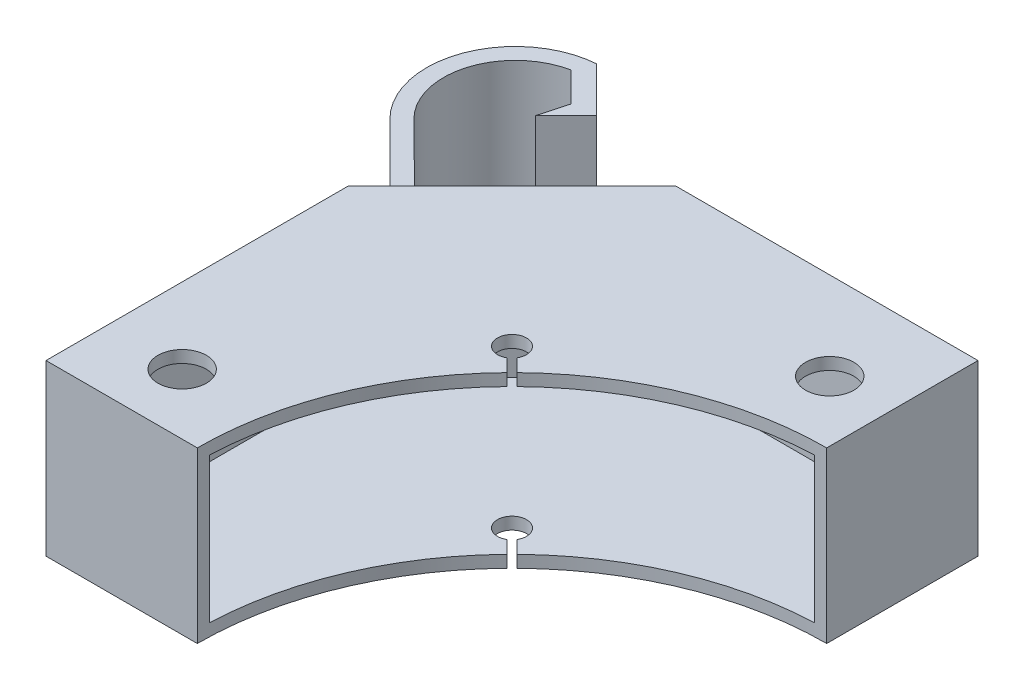
SolidWorks part; units mm, degrees
ref_plane "Front Plane" through (0, 0, 0) normal (0, 0, 1) x (1, 0, 0)
ref_plane "Top Plane" through (0, 0, 0) normal (0, 1, 0) x (1, 0, 0)
ref_plane "Right Plane" through (0, 0, 0) normal (1, 0, 0) x (0, 0, -1)
sketch "Sketch1" plane through (0, 0, 0) normal (0, 1, 0) x (1, 0, 0)
  line L0 (0, 0) -> (0, 50)
  line L1 (0, 0) -> (25, 0)
  line L2 (27, 77) -> (0, 50)
  line L3 (27, 77) -> (77, 77)
  line L4 (77, 77) -> (77, 52)
  line L5 (40.6572, 37.1914) -> (39.8086, 36.3428) construction
  line L6 (39.8086, 36.3428) -> (37.6873, 38.4642)
  line L7 (40.6572, 37.1914) -> (38.5358, 39.3127)
  line L8 (77, 52) -> (77, 0) construction
  line L9 (25, 0) -> (77, 0) construction
  arc A0 (39.8086, 36.3428) -> (25, 0) centre (77, 0) ccw
  arc A1 (40.6572, 37.1914) -> (77, 52) centre (77, 0) cw
  arc A2 (37.6873, 38.4642) -> (38.5358, 39.3127) centre (36.4684, 40.5316) cw
  dimension "D2" = 52
  dimension "D11" = 2.4
  dimension "D5" = 135
  dimension "D6" = 1.2
  dimension "D9" = 3
  dimension "D7" = 25
extrude "Boss-Extrude1" add sketch "Sketch1" along normal blind 28
shell "Shell1" thickness 2 removed face at (58.1033, 14, -46.3757) removed face at (30.6243, 14, -18.8967)
ref_plane "Plane3" through (0, 14, 0) normal (0, 1, 0) x (1, 0, 0)
sketch "Sketch7" plane through (0, 14, 0) normal (0, 1, 0) x (1, 0, 0)
  line L0 (0, 0) -> (0, 50)
  line L1 (0, 0) -> (25, 0)
  line L2 (25, 75) -> (0, 50)
  line L3 (25, 75) -> (75, 75)
  line L4 (75, 75) -> (75, 50)
  line L5 (40.431, 36.1246) -> (38.8754, 34.569) construction
  line L6 (38.8754, 34.569) -> (36.7541, 36.6903)
  line L7 (40.431, 36.1246) -> (38.3097, 38.2459)
  line L8 (75, 50) -> (75, 0) construction
  line L9 (25, 0) -> (75, 0) construction
  arc A0 (38.8754, 34.569) -> (25, 0) centre (75, 0) ccw
  arc A1 (40.431, 36.1246) -> (75, 50) centre (75, 0) cw
  arc A2 (36.7541, 36.6903) -> (38.3097, 38.2459) centre (36.1847, 38.8153) cw
  dimension "D5" = 135
  dimension "D2" = 50
  dimension "D11" = 2.2
  dimension "D6" = 2.2
  dimension "D7" = 25
  dimension "D9" = 3
sketch "Sketch9" plane through (0, 14, 0) normal (0, 1, 0) x (1, 0, 0)
  circle A0 centre (36.1847, 38.8153) radius 6.4
  dimension "D1" = 12.8
extrude "Cut-Extrude1" cut sketch "Sketch9" against normal blind 12 and the other way blind 12
ref_plane "Plane4" through (0, 28, 0) normal (0, 1, 0) x (1, 0, 0)
sketch "Sketch12" plane through (0, 28, 0) normal (0, 1, 0) x (1, 0, 0)
  line L2 (77, 52) -> (77, 77) construction
  line L5 (40.431, 36.1246) -> (38.8754, 34.569) construction
  line L8 (75, 50) -> (75, 0) construction
  line L9 (25, 0) -> (75, 0) construction
  line L10 (77, 62.5) -> (67, 62.5) construction
  line L11 (12.5, 0) -> (12.5, 10) construction
  circle A3 centre (67, 62.5) radius 4
  circle A4 centre (12.5, 10) radius 4
  dimension "D3" = 8
  dimension "D10" = 8
  dimension "D6" = 2.2
  dimension "D4" = 10
extrude "Cut-Extrude3" cut sketch "Sketch12" against normal blind 2
sketch "Sketch17" plane through (-25, 0, -25) normal (-0.7071, 0, -0.7071) x (-0.7071, 0, 0.7071)
  line L8 (-72.5391, 1) -> (-36.3553, 1)
  line L9 (-36.3553, 1) -> (-36.3553, 27)
  line L10 (-36.3553, 27) -> (-72.5391, 27)
  line L11 (-72.5391, 27) -> (-72.5391, 1)
  line L12 (-72.5391, 1) -> (-36.3553, 1)
  line L13 (-36.3553, 1) -> (-36.3553, 27)
  line L14 (-36.3553, 27) -> (-72.5391, 27)
  line L15 (-72.5391, 27) -> (-72.5391, 1)
  dimension "D1" = 1
extrude "Boss-Extrude2" add sketch "Sketch17" along normal blind 30 contours L14 L15 L12 L13
sketch "Sketch19" plane through (0, 27, 0) normal (0, 1, 0) x (1, 0, 0)
  line L0 (-7.1766, 64.0016) -> (3.4125, 53.4125)
  line L1 (0.7071, 50.7071) -> (26.2929, 76.2929) construction
  line L2 (2.0478, 88.9524) -> (9.449, 81.5512)
  line L3 (9.449, 81.5512) -> (4.4104, 76.5127)
  line L4 (4.4104, 76.5127) -> (5.671, 81.0865)
  line L5 (5.671, 81.0865) -> (0.8073, 85.9502)
  line L6 (-5.1535, 65.9471) -> (5.4457, 55.4457)
  line L7 (3.4125, 53.4125) -> (0.7071, 50.7071)
  line L8 (0.7071, 50.7071) -> (-20.5061, 71.9203)
  line L9 (-20.5061, 71.9203) -> (5.0797, 97.5061)
  line L10 (5.0797, 97.5061) -> (26.2929, 76.2929)
  line L11 (26.2929, 76.2929) -> (5.4457, 55.4457)
  arc A0 (-7.1766, 64.0016) -> (2.0478, 88.9524) centre (3.1764, 74.3546) cw
  arc A1 (-5.1535, 65.9471) -> (0.8073, 85.9502) centre (3.1764, 74.3546) cw
  point P11 (3.1764, 74.3546)
  dimension "D1" = 3
sketch "Sketch22" plane through (0, 27, 0) normal (0, 1, 0) x (1, 0, 0)
  line L0 (3.4125, 53.4125) -> (5.4457, 55.4457)
split line "Split Line2"
extrude "Cut-Extrude14" cut sketch "Sketch19<7>" against normal blind 30
sketch "Sketch19<7>" plane through (0, 27, 0) normal (0, 1, 0) x (1, 0, 0) same geometry as "Sketch19"
equation "\"innerRadius\"= 52mm"
equation "\"addedDimension\"= 25mm"
equation "\"D2@Sketch1\"=\"innerRadius\""
equation "\"thinConnectorWidth\"= 1.2mm"
equation "\"D6@Sketch1\"=\"thinConnectorWidth\""
equation "\"D9@Sketch1\"=\"thinConnectorLength\""
equation "\"thinConnectorLength\"= 3mm"
equation "\"connectorCircleRadius\"= 2.4mm"
equation "\"D11@Sketch1\"=\"connectorCircleRadius\""
equation "\"D7@Sketch1\"=\"addedDimension\""
equation "\"shellWidth\"= 2mm"
equation "\"D1@Shell1\"=\"shellWidth\""
equation "\"extrusionHeight\"= 28mm"
equation "\"D1@Boss-Extrude1\"=\"extrusionHeight\""
equation "\"D1@Sketch9\"=2*(\"connectorCircleRadius\"+\"thinConnectorLength\") + \"shellWidth\""
equation "\"D2@Cut-Extrude1\"=\"extrusionHeight\"/2 - \"shellWidth\""
equation "\"D1@Cut-Extrude1\"=\"extrusionHeight\"/2-\"shellWidth\""
equation "\"magnetHoleDiam\"= 26.5mm"
equation "\"throughHoleRadius\"= 4mm"
equation "\"D3@Sketch12\"=\"throughHoleRadius\"*2"
equation "\"D10@Sketch12\"=\"throughHoleRadius\"*2"
equation "\"throughHoleDistanceFromEdge\"= 10mm"
equation "\"D1@Cut-Extrude3\"=\"shellWidth\""
